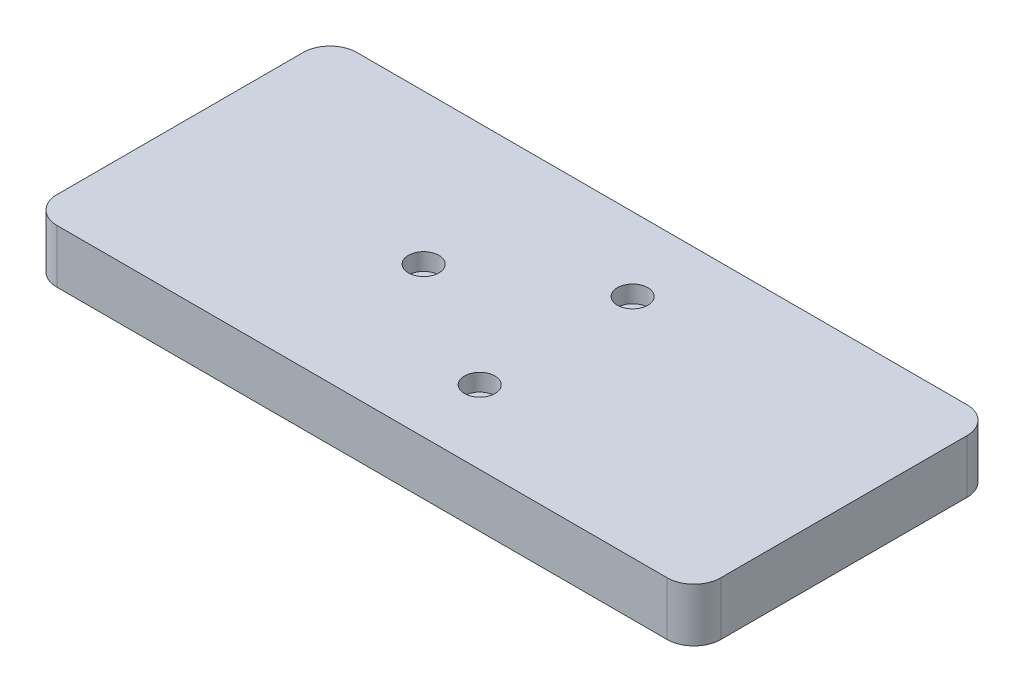
SolidWorks part; units mm, degrees
ref_plane "Ebene vorne" through (0, 0, 0) normal (0, 0, 1) x (1, 0, 0)
ref_plane "Ebene oben" through (0, 0, 0) normal (0, 1, 0) x (1, 0, 0)
ref_plane "Ebene rechts" through (0, 0, 0) normal (1, 0, 0) x (0, 0, -1)
sketch "Skizze1" plane through (0, 0, 0) normal (0, 1, 0) x (1, 0, 0)
  line L0 (0, 116.3752) -> (0, -108.2302) construction
  line L1 (-102.1831, 0) -> (110.575, 0) construction
  line L2 (-62, -28) -> (-62, 28)
  line L3 (-62, 28) -> (62, 28)
  line L4 (62, -28) -> (62, 28)
  line L5 (-62, -28) -> (62, -28)
  point P9 (0, 28)
  point P10 (0, -28)
  point P12 (62, 0)
  point P13 (-62, 0)
  dimension "D1" = 124
  dimension "D2" = 56
extrude "Aufsatz-Linear austragen1" add sketch "Skizze1" along normal blind 10
ref_axis "Achse1" through (0, -0.5, 0) along (0, 1, 0)
fillet "Verrundung1" radius 5 4 edges at (-62, 5, -28) (62, 5, -28) (62, 5, 28) (-62, 5, 28)
sketch "Skizze2" plane through (0, 10, 0) normal (0, 1, 0) x (1, 0, 0)
  line L0 (0, 67.8707) -> (0, -65.3386) construction
  line L1 (-92.1366, 0) -> (92.1366, 0) construction
  line L2 (0, 0) -> (21.3849, 37.0397) construction
  circle A0 centre (0, 0) radius 16.5 construction
  circle A1 centre (-16.5, 0) radius 1.55
  circle A2 centre (8.25, 14.2894) radius 1.55
  circle A3 centre (8.25, -14.2894) radius 1.55
  dimension "D1" = 3.1
  dimension "D2" = 33
  dimension "D3" = 120
extrude "Schnitt-Linear austragen1" cut sketch "Skizze2" against normal up to next
sketch "Skizze3" plane through (0, 10, 0) normal (0, 1, 0) x (1, 0, 0)
  circle A0 centre (8.25, 14.2894) radius 2.85
  circle A1 centre (-16.5, 0) radius 2.85
  circle A2 centre (8.25, -14.2894) radius 2.85
  dimension "D1" = 5.7
extrude "Schnitt-Linear austragen2" cut sketch "Skizze3" against normal offset from surface (3.2 mm away) 6.8 up to face at (-16.5, 0, 1.55)
